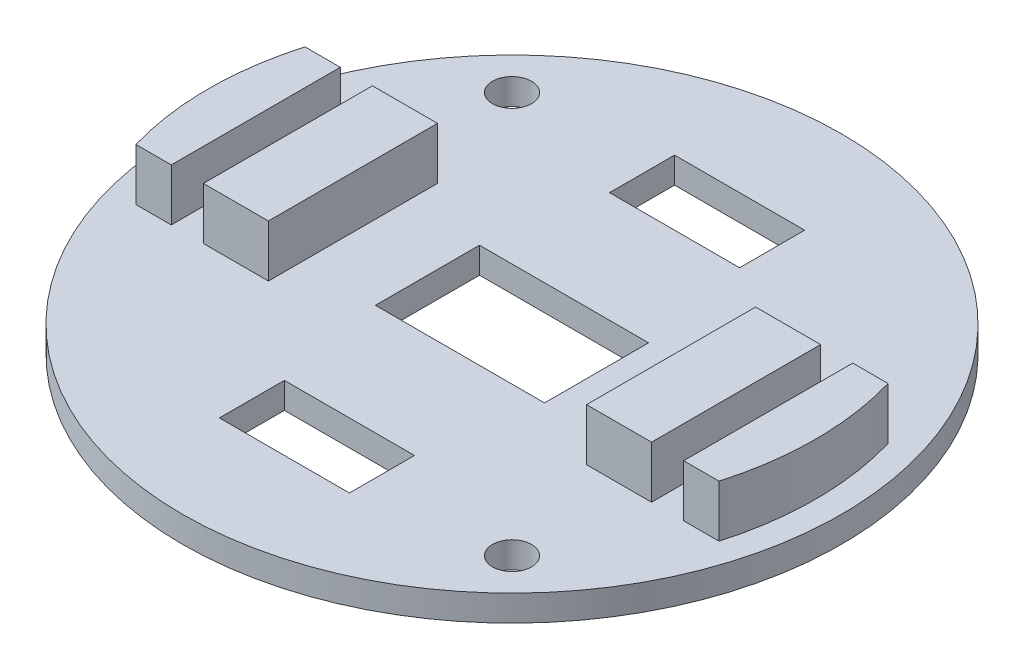
SolidWorks part; units mm, degrees
ref_plane "Front Plane" through (0, 0, 0) normal (0, 0, 1) x (1, 0, 0)
ref_plane "Top Plane" through (0, 0, 0) normal (0, 1, 0) x (1, 0, 0)
ref_plane "Right Plane" through (0, 0, 0) normal (1, 0, 0) x (0, 0, -1)
sketch "Sketch1" plane through (0, 0, 0) normal (0, 1, 0) x (1, 0, 0)
  circle A0 centre (0, 0) radius 25.34
  dimension "D1" = 50.68
extrude "Boss-Extrude1" add sketch "Sketch1" along normal blind 2
sketch "Sketch6" plane through (0, 2, 0) normal (0, 1, 0) x (1, 0, 0)
  circle A0 centre (0, 0) radius 23.34
  circle A1 centre (0, 0) radius 25.34
  circle A2 centre (0, 0) radius 25.34
  dimension "D1" = 0
  dimension "D2" = 2
sketch "Sketch2" plane through (0, 2, 0) normal (0, 1, 0) x (1, 0, 0)
  line L0 (-17.23, 0) -> (17.23, 0) construction
  line L1 (0, 32.0817) -> (0, -28.5676) construction
  line L10 (12.23, -6.5) -> (17.23, -6.5)
  line L11 (12.23, -6.5) -> (12.23, 6.5)
  line L12 (12.23, 6.5) -> (17.23, 6.5)
  line L13 (17.23, -6.5) -> (17.23, 6.5)
  line L26 (22.4166, 6.5) -> (19.7, 6.5)
  line L27 (19.7, 6.5) -> (19.7, -6.5)
  line L32 (19.7, -6.5) -> (22.4166, -6.5)
  line L33 (-19.7, -6.5) -> (-22.4166, -6.5)
  line L34 (-12.23, 6.5) -> (-17.23, 6.5)
  line L35 (-17.23, -6.5) -> (-17.23, 6.5)
  line L36 (-12.23, -6.5) -> (-17.23, -6.5)
  line L37 (-12.23, -6.5) -> (-12.23, 6.5)
  line L38 (-22.4166, 6.5) -> (-19.7, 6.5)
  line L39 (-19.7, 6.5) -> (-19.7, -6.5)
  circle A2 centre (0, 0) radius 23.34 construction
  arc A3 (-22.4166, 6.5) -> (-22.4166, -6.5) centre (0, 0) ccw
  arc A4 (22.4166, -6.5) -> (22.4166, 6.5) centre (0, 0) ccw
  point P2 (0, 0)
  point P7 (17.23, 0)
  dimension "D1" = 2.47
  dimension "D2" = 39.4
  dimension "D3" = 5
  dimension "D4" = 13
extrude "Boss-Extrude2" add sketch "Sketch2" along normal blind 4
sketch "Sketch3" plane through (0, 2, 0) normal (0, 1, 0) x (1, 0, 0)
  line L0 (-15.422, 15.422) -> (15.422, -15.422) construction
  line L1 (-43.7486, 0) -> (48.7139, 0) construction
  circle A0 centre (-15.422, 15.422) radius 1.5
  circle A1 centre (15.422, -15.422) radius 1.5
  point P6 (0, 0)
  dimension "D3" = 3
  dimension "D1" = 45
  dimension "D2" = 43.62
extrude "Cut-Extrude1" cut sketch "Sketch3" against normal through all
sketch "Sketch4" plane through (0, 2, 0) normal (0, 1, 0) x (1, 0, 0)
  line L0 (-60.1037, 0) -> (65.0626, 0) construction
  line L1 (5, 17.5) -> (-5, 17.5)
  line L2 (5, 17.5) -> (5, 12.5)
  line L3 (5, 12.5) -> (-5, 12.5)
  line L4 (-5, 17.5) -> (-5, 12.5)
  line L5 (5, 17.5) -> (-5, 12.5) construction
  line L6 (5, 12.5) -> (-5, 17.5) construction
  line L7 (5, -12.5) -> (-5, -17.5) construction
  line L8 (5, -17.5) -> (-5, -12.5) construction
  line L9 (-5, -17.5) -> (-5, -12.5)
  line L10 (5, -12.5) -> (-5, -12.5)
  line L11 (5, -17.5) -> (5, -12.5)
  line L12 (5, -17.5) -> (-5, -17.5)
  line L14 (6.5, 4) -> (-6.5, 4)
  line L15 (6.5, 4) -> (6.5, -4)
  line L16 (6.5, -4) -> (-6.5, -4)
  line L17 (-6.5, 4) -> (-6.5, -4)
  line L18 (6.5, 4) -> (-6.5, -4) construction
  line L19 (6.5, -4) -> (-6.5, 4) construction
  point P0 (0, 15)
  point P12 (0, -15)
  point P13 (0, 0)
  dimension "D1" = 10
  dimension "D2" = 5
  dimension "D3" = 15
  dimension "D4" = 13
  dimension "D5" = 8
extrude "Cut-Extrude2" cut sketch "Sketch4" against normal through all
